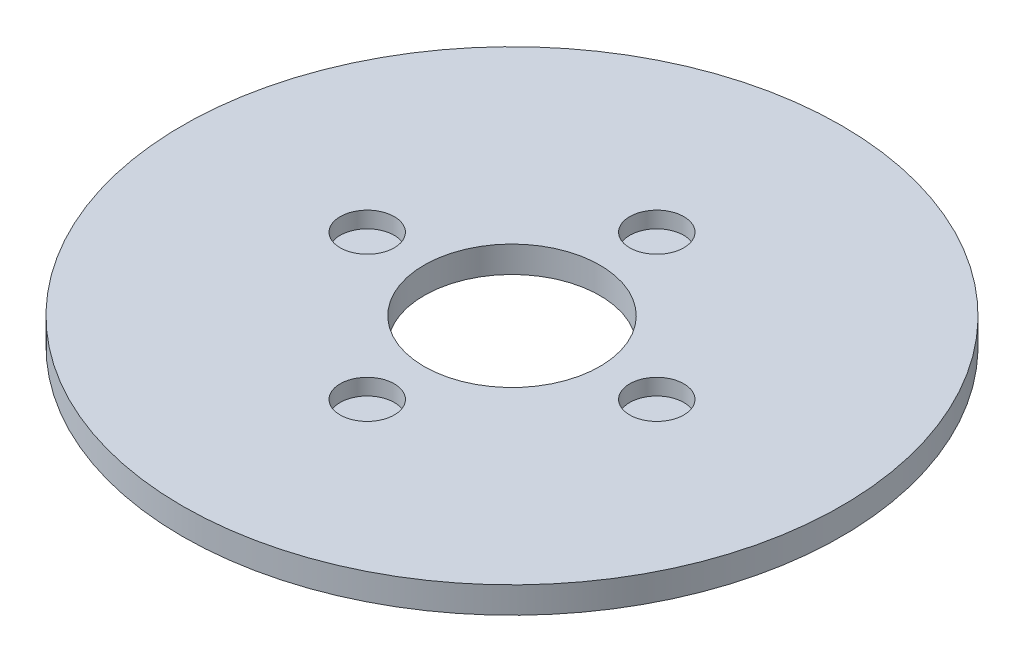
SolidWorks part; units mm, degrees
ref_plane "Front Plane" through (0, 0, 0) normal (0, 0, 1) x (1, 0, 0)
ref_plane "Top Plane" through (0, 0, 0) normal (0, 1, 0) x (1, 0, 0)
ref_plane "Right Plane" through (0, 0, 0) normal (1, 0, 0) x (0, 0, -1)
sketch "Sketch1" plane through (0, 0, 0) normal (0, 1, 0) x (1, 0, 0)
  circle A0 centre (0, 0) radius 75
  dimension "FLANGE_OD" = 150
extrude "Boss-Extrude1" add sketch "Sketch1" along normal blind 6
sketch "Sketch2" plane through (0, 0, 0) normal (0, 1, 0) x (1, 0, 0)
  circle A0 centre (0, 0) radius 20
  dimension "BORE_D" = 40
extrude "Cut-Extrude1" cut sketch "Sketch2" along normal through all
sketch "Sketch3" plane through (0, 6, 0) normal (0, 1, 0) x (1, 0, 0)
  circle A0 centre (0, 0) radius 32.949 construction
  circle A1 centre (-32.949, 0) radius 6.1545
  dimension "BOLT_D" = 12.309
  dimension "BOLT_PCD" = 65.898
extrude "Cut-Extrude2" cut sketch "Sketch3" against normal blind 3.69
pattern_circular "CirPattern1" count 4 over 360 about axis through (0, 0, 0) along (0, 1, 0) of "Cut-Extrude2"
